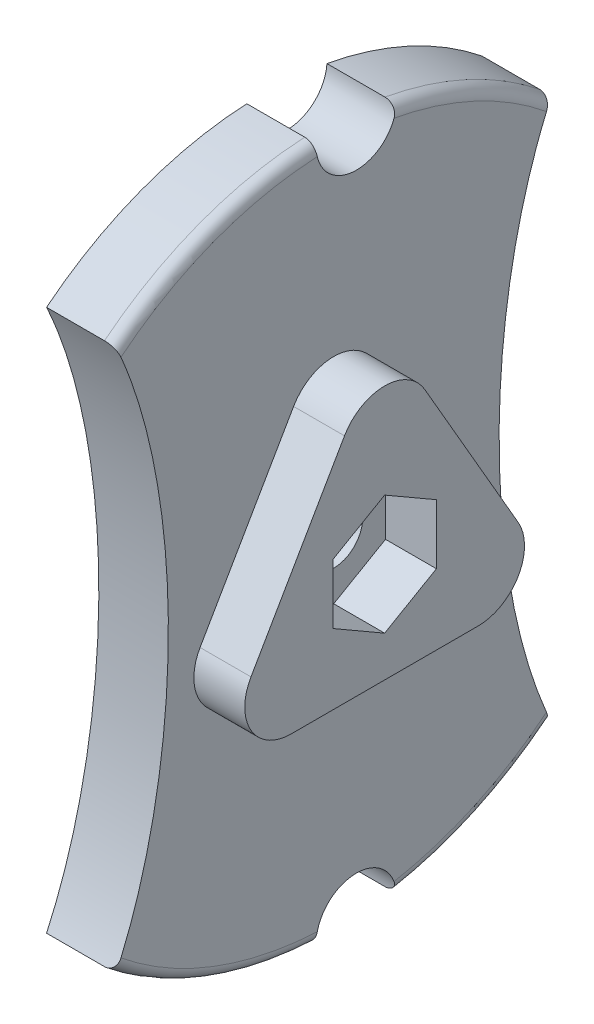
SolidWorks part; units mm, degrees
ref_plane "Front Plane" through (0, 0, 0) normal (0, 0, 1) x (1, 0, 0)
ref_plane "Top Plane" through (0, 0, 0) normal (0, 1, 0) x (1, 0, 0)
ref_plane "Right Plane" through (0, 0, 0) normal (1, 0, 0) x (0, 0, -1)
sketch "Sketch2" plane through (0, 0, 0) normal (1, 0, 0) x (0, 0, -1)
  line L0 (55, 0) -> (-55, 0) construction
  arc A0 (6.8776, -37.4741) -> (6.8776, 37.4741) centre (0, 0) ccw
  circle A1 centre (0, 0) radius 3.175
  arc A2 (-1.9043, -38.0524) -> (6.8776, -37.4741) centre (2.4867, -37.7632) cw
  arc A3 (-1.9043, 38.0524) -> (6.8776, 37.4741) centre (2.4867, 37.7632) ccw
  arc A4 (-1.9043, 38.0524) -> (-1.9043, -38.0524) centre (0, 0) ccw
  dimension "D1" = 76.2
  dimension "D2" = 6.35
extrude "Boss-Extrude1" add sketch "Sketch2" along normal blind 7.62
sketch "Sketch3" plane through (7.62, 0, 0) normal (1, 0, 0) x (0, 0, -1)
  line L0 (-5.675, 3.2765) -> (-5.675, -3.2765)
  line L1 (19.05, -10.9985) -> (0, 21.997)
  line L2 (0, 21.997) -> (-19.05, -10.9985)
  line L3 (-19.05, -10.9985) -> (19.05, -10.9985)
  line L4 (5.675, -3.2765) -> (5.675, 3.2765)
  line L5 (5.675, 3.2765) -> (0, 6.5529)
  line L6 (0, 6.5529) -> (-5.675, 3.2765)
  line L7 (-5.675, -3.2765) -> (0, -6.5529)
  line L8 (0, -6.5529) -> (5.675, -3.2765)
  circle A0 centre (0, 0) radius 10.9985 construction
  circle A1 centre (0, 0) radius 5.675 construction
  dimension "D1" = 11.35
  dimension "D2" = 38.1
extrude "Boss-Extrude2" add sketch "Sketch3" along normal blind 5.58
fillet "Fillet1" radius 5.08 3 edges at (10.41, -10.9985, -19.05) (10.41, 21.997, 0) (10.41, -10.9985, 19.05)
fillet "Fillet3" radius 1.27 2 edges at (7.62, 0, -38.1) (7.62, 0, 38.1)
sketch "Sketch4" plane through (0, 0, 0) normal (-1, 0, 0) x (0, 0, 1)
  arc A0 (-6.8776, 37.4741) -> (-6.8776, -37.4741) centre (0, 0) ccw construction
  ellipse E0 centre (-38.1, 0) end of major axis (-38.1, -42.3764) minor radius 19.9746
  point P1 (0, 0)
  point P7 (-19.6243, 0)
  point P11 (0, 0)
  point P12 (0, 0)
  point P13 (-18.1254, 0)
extrude "Cut-Extrude1" cut sketch "Sketch4" against normal through all
mirror "Mirror1" about plane through (0, 0, 0) normal (0, 0, 1) of "Cut-Extrude1"
